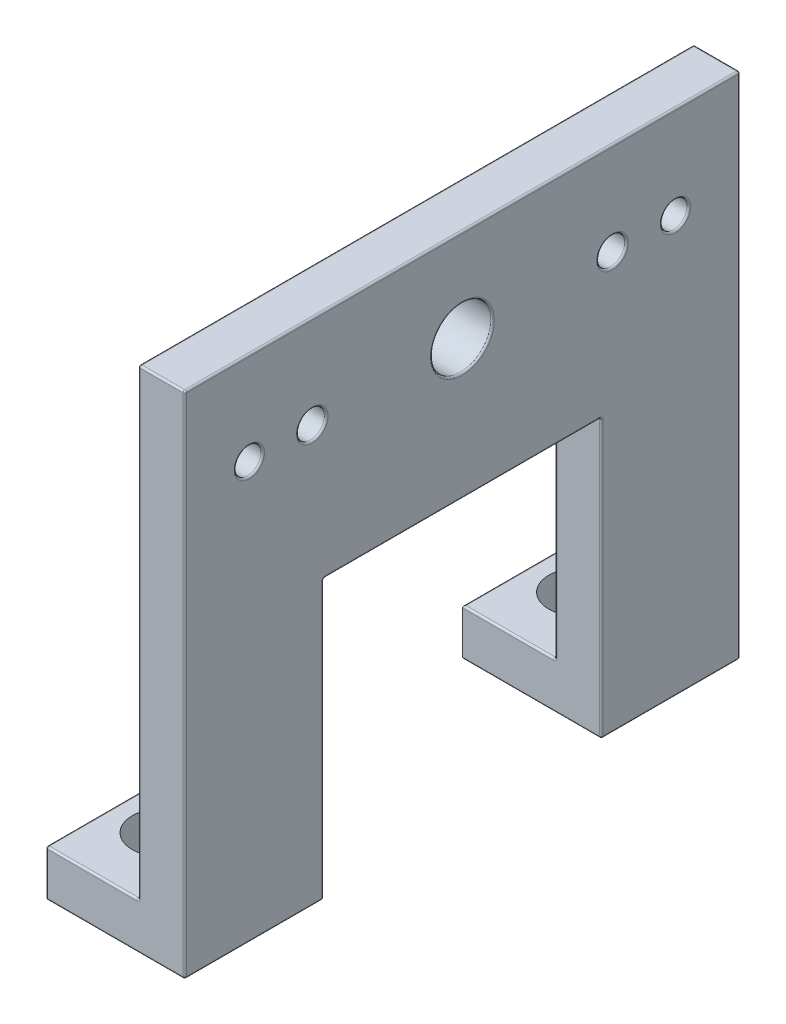
SolidWorks part; units mm, degrees
ref_plane "Front Plane" through (0, 0, 0) normal (0, 0, 1) x (1, 0, 0)
ref_plane "Top Plane" through (0, 0, 0) normal (0, 1, 0) x (1, 0, 0)
ref_plane "Right Plane" through (0, 0, 0) normal (1, 0, 0) x (0, 0, -1)
sketch "Sketch1" plane through (0, 0, 0) normal (0, 0, 1) x (1, 0, 0)
  line L1 (0, 0) -> (15, 0)
  line L2 (0, 0) -> (0, 5)
  line L3 (0, 5) -> (10, 5)
  line L6 (12.5, 0) -> (12.5, 55) construction
  line L7 (15, 55) -> (10, 55)
  line L8 (10, 5) -> (10, 55)
  line L10 (15, 5) -> (15, 55)
  line L11 (15, 5) -> (15, 0)
  dimension "D1" = 5
  dimension "D2" = 5
  dimension "D3" = 50
  dimension "D4" = 15
extrude "Boss-Extrude1" add sketch "Sketch1" along normal blind 60
sketch "Sketch2" plane through (15, 0, 0) normal (1, 0, 0) x (0, 0, -1)
  line L4 (0, 0) -> (0, 55)
  line L5 (0, 55) -> (-60, 55)
  line L6 (-60, 55) -> (-60, 0)
  line L7 (-60, 0) -> (0, 0)
  line L8 (0, 0) -> (0, 55) construction
  line L9 (0, 55) -> (-60, 55) construction
  line L10 (-60, 55) -> (-60, 0) construction
  line L12 (0, 0) -> (0, 55)
  line L13 (0, 55) -> (-60, 55)
  line L14 (-60, 55) -> (-60, 0)
  line L15 (-60, 0) -> (0, 0)
  line L20 (0, 0) -> (0, 55) construction
  line L21 (0, 55) -> (-60, 55) construction
  line L22 (-60, 55) -> (-60, 0) construction
  line L23 (-60, 0) -> (0, 0) construction
  circle A0 centre (-30, 45) radius 3.25
  circle A1 centre (-53.0125, 45) radius 1.435 construction
  circle A2 centre (-46.215, 45) radius 1.5 construction
  circle A3 centre (-13.785, 45) radius 1.5 construction
  circle A4 centre (-6.9875, 45) radius 1.435 construction
  circle A5 centre (-53.0125, 45) radius 1.435
  circle A6 centre (-46.215, 45) radius 1.5
  circle A7 centre (-13.785, 45) radius 1.5
  circle A8 centre (-6.9875, 45) radius 1.435
  point P2 (-30, 55)
  point P4 (-60, 27.5)
  point P6 (-30, 45)
  dimension "D4" = 6.5
  dimension "D2" = 0
  dimension "D3" = 10
  dimension "D1" = 0
extrude "Cut-Extrude1" cut sketch "Sketch2" against normal through all
sketch "Sketch3" plane through (0, 0, 0) normal (0, 0, -1) x (-1, 0, 0)
  line L0 (-15, 30) -> (-10, 30)
  line L6 (0, 0) -> (0, 5)
  line L7 (0, 5) -> (-10, 5)
  line L8 (-10, 5) -> (-10, 55)
  line L9 (-10, 55) -> (-15, 55)
  line L10 (-15, 55) -> (-15, 0)
  line L11 (-15, 0) -> (0, 0)
  line L12 (0, 0) -> (0, 5)
  line L13 (0, 5) -> (-10, 5)
  line L14 (-10, 5) -> (-10, 30)
  line L16 (-15, 30) -> (-15, 0)
  line L17 (-15, 0) -> (0, 0)
  dimension "D2" = 30
  dimension "D1" = 0
extrude "Cut-Extrude2" cut sketch "Sketch3" against normal blind 30 from offset 15 offset against normal yes
fillet "Fillet16" radius 0.2 44 edges at (5, 5, 15) (0, 5, 7.5) (0, 5, 52.5) (5, 5, 45) (12.5, 30, 45) (12.5, 30, 15) (0, 0, 52.5) (7.5, 0, 45) (0, 0, 7.5) (7.5, 0, 15) (5, 5, 60) (12.5, 55, 60) (7.5, 0, 60) (0, 2.5, 60) (7.5, 0, 0) (12.5, 55, 0) (5, 5, 0) (0, 2.5, 0) (15, 0, 52.5) (15, 27.5, 60) (15, 55, 30) (15, 27.5, 0) (15, 0, 7.5) (15, 15, 15) (15, 30, 30) (15, 15, 45) (15, 46.435, 6.9875) (15, 46.5, 13.785) (15, 46.5, 46.215) (15, 46.435, 53.0125) (15, 48.25, 30) (10, 30, 30) (10, 17.5, 15) (10, 5, 7.5) (10, 30, 0) (10, 55, 30) (10, 30, 60) (10, 5, 52.5) (10, 17.5, 45) (10, 46.435, 6.9875) (10, 46.5, 13.785) (10, 46.5, 46.215) (10, 46.435, 53.0125) (10, 48.25, 30)
sketch "Sketch4" plane through (0, 5, 0) normal (0, 1, 0) x (1, 0, 0)
  line L4 (0.2, -0.2) -> (0.2, -14.8)
  line L5 (0.2, -14.8) -> (9.8, -14.8)
  line L6 (9.8, -14.8) -> (9.8, -0.2)
  line L7 (9.8, -0.2) -> (0.2, -0.2)
  line L8 (0.2, -0.2) -> (0.2, -14.8) construction
  line L9 (0.2, -14.8) -> (9.8, -14.8) construction
  line L10 (9.8, -14.8) -> (9.8, -0.2) construction
  line L11 (9.8, -0.2) -> (0.2, -0.2) construction
  line L12 (9.8, -45.2) -> (0.2, -45.2)
  line L13 (0.2, -45.2) -> (0.2, -59.8)
  line L14 (0.2, -59.8) -> (9.8, -59.8)
  line L15 (9.8, -59.8) -> (9.8, -45.2)
  line L16 (9.8, -45.2) -> (0.2, -45.2) construction
  line L17 (0.2, -45.2) -> (0.2, -59.8) construction
  line L18 (0.2, -59.8) -> (9.8, -59.8) construction
  line L19 (9.8, -59.8) -> (9.8, -45.2) construction
  circle A0 centre (5, -7.5) radius 3.175
  circle A1 centre (5, -52.5) radius 3.175
  point P6 (9.8, -7.5)
  point P8 (5, -0.2)
  point P10 (9.8, -52.5)
  point P11 (5, -45.2)
  point P16 (0, 0)
  point P17 (0, 0)
  point P18 (0, 0)
  point P19 (0, 0)
  dimension "D3" = 6.35
  dimension "D1" = 0
  dimension "D2" = 0
extrude "Cut-Extrude3" cut sketch "Sketch4" against normal through all
